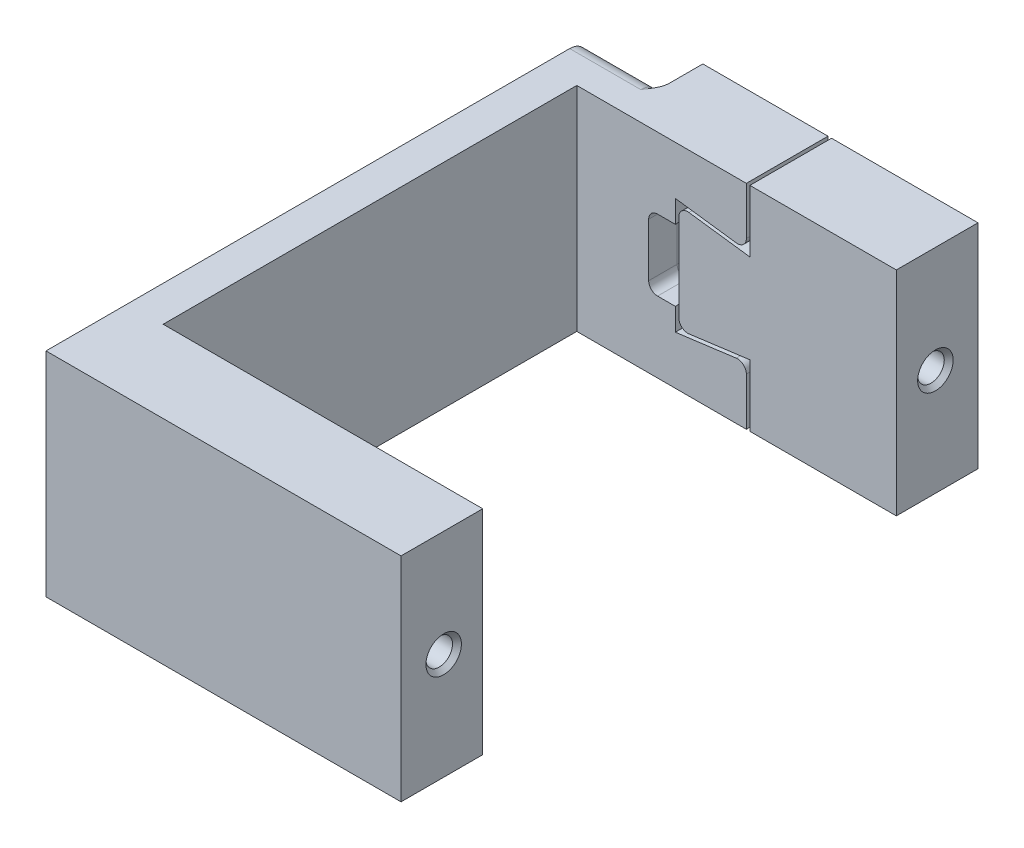
SolidWorks part; units mm, degrees
ref_plane "Front Plane" through (0, 0, 0) normal (0, 0, 1) x (1, 0, 0)
ref_plane "Top Plane" through (0, 0, 0) normal (0, 1, 0) x (1, 0, 0)
ref_plane "Right Plane" through (0, 0, 0) normal (1, 0, 0) x (0, 0, -1)
sketch "Sketch1" plane through (0, 0, 0) normal (0, 1, 0) x (1, 0, 0)
  line L0 (0, 16.25) -> (0, 11.65)
  line L1 (0, 11.65) -> (-18, 11.65)
  line L2 (-18, 11.65) -> (-18, -11.65)
  line L3 (-18, -11.65) -> (0, -11.65)
  line L4 (0, -11.65) -> (0, -16.25)
  line L5 (0, -16.25) -> (-20, -16.25)
  line L6 (-20, -16.25) -> (-20, 16.25)
  line L7 (-20, 16.25) -> (0, 16.25)
  line L8 (-18, 0) -> (0, 0) construction
  dimension "D1" = 23.3
  dimension "D2" = 18
  dimension "D3" = 4.6
  dimension "D4" = 2
extrude "Boss-Extrude1" add sketch "Sketch1" along normal mid plane 12
sketch "Sketch4" plane through (0, 0, 0) normal (1, 0, 0) x (0, 0, -1)
  line L0 (-13.85, 0) -> (13.85, 0) construction
  circle A0 centre (13.85, 0) radius 0.75
  circle A1 centre (-13.85, 0) radius 0.75
  point P4 (0, 0)
  dimension "D1" = 1.5
  dimension "D2" = 27.7
extrude "Cut-Extrude3" cut sketch "Sketch4" against normal blind 8
chamfer "Chamfer1" distance 0.25 angle 45 2 edges at (0, 0, -14.6) (0, 0, 13.1)
sketch "Sketch2" plane through (0, 0, -16.25) normal (0, 0, -1) x (-1, 0, 0)
  line L0 (18, 6) -> (18, -6) construction
  line L1 (18, 6) -> (18, -6) construction
  line L2 (13.2, 2) -> (13.2, -2) construction
  line L3 (12.45, 2) -> (13.95, 2)
  line L4 (12.45, 2) -> (12.45, -2)
  line L5 (12.45, -2) -> (13.95, -2)
  line L6 (13.95, 2) -> (13.95, -2)
  line L7 (13.2, 0) -> (18, 0) construction
  dimension "D1" = 4.8
  dimension "D2" = 1.5
  dimension "D3" = 4
extrude "Cut-Extrude1" cut sketch "Sketch2" against normal up to next
sketch "Sketch5" plane through (0, 0, -16.25) normal (0, 0, -1) x (-1, 0, 0)
  line L0 (20, 6) -> (20, -6) construction
  line L1 (13.95, 2) -> (20, 2)
  line L2 (13.95, 2) -> (13.95, -2)
  line L3 (13.95, -2) -> (20, -2)
  line L4 (20, 2) -> (20, -2)
extrude "Cut-Extrude5" cut sketch "Sketch5" against normal blind 2
sketch "Sketch6" plane through (0, -6, 0) normal (0, -1, 0) x (1, 0, 0)
  line L0 (-15.5, -14.25) -> (-15.5, -16.25)
  line L6 (-12.45, -11.65) -> (-13.95, -11.65)
  line L7 (-13.95, -11.65) -> (-13.95, -14.25)
  line L8 (-13.95, -14.25) -> (-20, -14.25)
  line L9 (-20, -14.25) -> (-20, -16.25)
  line L10 (-20, -16.25) -> (-12.45, -16.25)
  line L11 (-12.45, -16.25) -> (-12.45, -11.65)
  line L14 (-15.5, -14.25) -> (-20, -14.25)
  line L15 (-20, -14.25) -> (-20, -16.25)
  line L16 (-20, -16.25) -> (-15.5, -16.25)
  dimension "D2" = 4.5
  dimension "D1" = 0
extrude "Cut-Extrude6" cut sketch "Sketch6" against normal through all
fillet "Fillet7" radius 1 3 edges at (-13.95, 0, -14.25) (-17.75, 6, -14.25) (-17.75, -6, -14.25)
sketch "Sketch3" plane through (0, 0, -16.25) normal (0, 0, -1) x (-1, 0, 0)
  line L0 (8.45, -6) -> (8.45, -2.7367)
  line L1 (0, -6) -> (15.5, -6) construction
  line L2 (8.45, -2.7367) -> (12.45, -3.2633)
  line L3 (12.45, -3.2633) -> (12.45, 3.2633)
  line L4 (12.45, 3.2633) -> (8.45, 2.7367)
  line L5 (8.45, 2.7367) -> (8.45, 6)
  line L6 (0, 6) -> (15.5, 6) construction
  line L7 (12.45, 0) -> (0, 0) construction
  line L9 (12.45, 2) -> (12.45, -2) construction
  line L10 (12.45, 3.2633) -> (12.45, 6) construction
  line L11 (12.45, 0) -> (8.45, 0) construction
  line L12 (8.45, 0) -> (8.45, 2.7367) construction
  line L13 (8.25, -6) -> (8.25, -2.5086)
  line L14 (8.25, -2.5086) -> (12.25, -3.0352)
  line L15 (12.25, -3.0352) -> (12.25, 3.0352)
  line L16 (12.25, 3.0352) -> (8.25, 2.5086)
  line L17 (8.25, 2.5086) -> (8.25, 6)
  line L18 (8.25, 6) -> (8.45, 6)
  line L19 (8.25, -6) -> (8.45, -6)
  dimension "D1" = 15
  dimension "D2" = 4
  dimension "D3" = 0.2
extrude "Cut-Extrude2" cut sketch "Sketch3" against normal up to next
fillet "Fillet9" radius 0.5 14 edges at (-13.95, -2, -12.45) (-13.95, 2, -12.45) (-8.45, -2.7367, -13.95) (-8.45, 2.7367, -13.95) (-15.225, -2, -14.25) (-14.2429, -2, -13.9571) (-15.225, 2, -14.25) (-14.2429, 2, -13.9571) (-15.5, 5.7071, -13.9571) (-15.5, -5.7071, -13.9571) (-15.5, -2, -15.25) (-15.5, 2, -15.25) (-15.5, 3.5, -14.25) (-15.5, -3.5, -14.25)
fillet "Fillet3" radius 0.5 2 edges at (-12.25, -3.0352, -13.95) (-12.25, 3.0352, -13.95)
sketch "Sketch9" plane through (0, 0, 0) normal (0, 1, 0) x (1, 0, 0)
  line L1 (-20, 5.25) -> (-23.5, 5.25)
  line L2 (-23.5, 5.25) -> (-23.5, 6.7)
  line L5 (-23.5, 6.7) -> (-20.5, 6.7)
  line L6 (0, 5.25) -> (-23.5, 5.25) construction
  line L7 (0, 0) -> (0, 5.25) construction
  line L8 (-20, 13.25) -> (-20, -16.25) construction
  line L9 (-20.5, 6.7) -> (-20.5, 7.25)
  line L10 (-20.5, 7.25) -> (-20, 7.25)
  line L11 (-20, 7.25) -> (-20, 5.25)
  point P3 (-20, 3.25)
  point P6 (0, 0)
  point P13 (-23.5, 3.8)
  point P15 (-23.5, 3.8)
  dimension "D1" = 5.25
  dimension "D2" = 0.5
  dimension "D3" = 2.9
  dimension "D4" = 3
  dimension "D5" = 4
revolve "Revolve2" add sketch "Sketch9" angle 360 about L6
